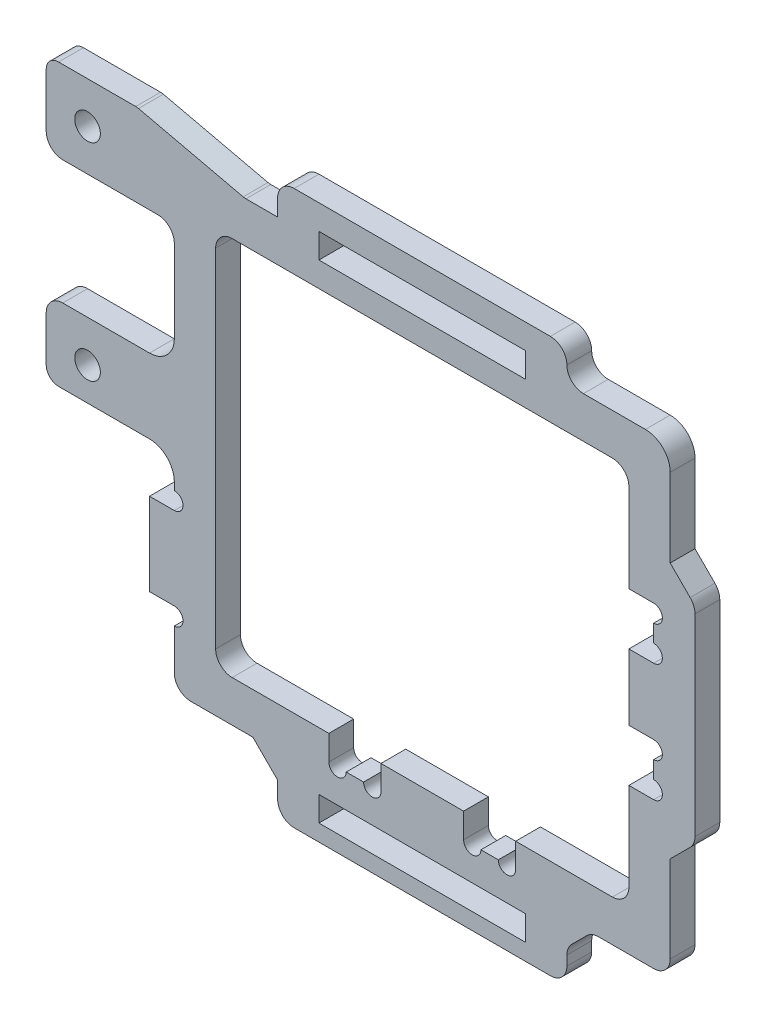
SolidWorks part; units mm, degrees
material "玻纤板"
ref_plane "前视基准面" through (0, 0, 0) normal (0, 0, 1) x (1, 0, 0)
ref_plane "上视基准面" through (0, 0, 0) normal (0, 1, 0) x (1, 0, 0)
ref_plane "右视基准面" through (0, 0, 0) normal (1, 0, 0) x (0, 0, -1)
sketch "草图1" plane through (0, 0, 0) normal (0, 0, 1) x (1, 0, 0)
  line L0 (-45.5, 31) -> (-45.5, 21)
  line L1 (25, -23) -> (11.3, -23)
  line L2 (25, -23) -> (25, -10.3)
  line L3 (25, 23) -> (-25, 23)
  line L4 (-25, -23) -> (-25, -11.2)
  line L5 (25, -23) -> (-25, 23) construction
  line L6 (25, 23) -> (-25, -23) construction
  line L7 (-45.5, 21) -> (-30, 21)
  line L8 (-30, 21) -> (-30, 15.2)
  line L9 (-30.5, 6) -> (-45.5, 6)
  line L11 (-35.5, -28) -> (-20.5, -28) construction
  line L12 (30, -28) -> (30, -23)
  line L13 (30, 28) -> (17.5, 28)
  line L14 (-5, -23) -> (-5, -26)
  line L15 (-5, -26) -> (-11.3, -26)
  line L16 (-11.3, -26) -> (-11.3, -23)
  line L17 (5, -23) -> (5, -26)
  line L18 (5, -26) -> (11.3, -26)
  line L19 (11.3, -26) -> (11.3, -23)
  line L20 (0, 0) -> (0, -12.9051) construction
  line L21 (-20.5, -28) -> (-17.5, -31) construction
  line L22 (-17.5, -31) -> (17.5, -31) construction
  line L23 (17.5, -31) -> (20.5, -28)
  line L24 (20.5, -28) -> (30, -28)
  line L25 (-11.3, -23) -> (-25, -23)
  line L26 (5, -23) -> (-5, -23)
  line L27 (25, 4) -> (28, 4)
  line L28 (28, 4) -> (28, 10.3)
  line L29 (28, 10.3) -> (25, 10.3)
  line L30 (25, -4) -> (28, -4)
  line L31 (28, -4) -> (28, -10.3)
  line L32 (28, -10.3) -> (25, -10.3)
  line L33 (0, 0) -> (16, 0) construction
  line L34 (30, 15.5) -> (33, 12.5)
  line L35 (33, 12.5) -> (33, -12.5)
  line L36 (33, -12.5) -> (30, -15.5)
  line L37 (25, 10.3) -> (25, 23)
  line L38 (25, -4) -> (25, 4)
  line L39 (30, 15.5) -> (30, 28)
  line L44 (-30, -9) -> (-33, -9)
  line L45 (-33, -9) -> (-33, -19)
  line L46 (-33, -19) -> (-30, -19)
  line L48 (17.5, 32) -> (17.5, 28)
  line L49 (17.5, 32) -> (-17.5, 32)
  line L50 (-17.5, 32) -> (-17.5, 28)
  line L51 (-17.5, 28) -> (-30, 28) construction
  line L52 (17.5, -31) -> (17.5, -35)
  line L53 (-12.5, 26) -> (12.5, 26)
  line L54 (-12.5, 26) -> (-12.5, 29)
  line L55 (-12.5, 29) -> (12.5, 29)
  line L56 (12.5, 26) -> (12.5, 29)
  line L57 (-12.5, 26) -> (12.5, 29) construction
  line L58 (-12.5, 29) -> (12.5, 26) construction
  line L59 (-12.5, -33) -> (12.5, -33)
  line L60 (-12.5, -33) -> (-12.5, -30)
  line L61 (-12.5, -30) -> (12.5, -30)
  line L62 (12.5, -33) -> (12.5, -30)
  line L63 (-12.5, -33) -> (12.5, -30) construction
  line L64 (-12.5, -30) -> (12.5, -33) construction
  line L65 (17.5, -35) -> (-17.5, -35)
  line L66 (-17.5, -35) -> (-17.5, -31) construction
  line L67 (30, -18) -> (42, -18) construction
  line L68 (42, -18) -> (39.1132, -23) construction
  line L69 (39.1132, -23) -> (29.9669, -23) construction
  line L70 (30, -18) -> (30, -15.5)
  line L71 (-45.5, 6) -> (-45.5, -3)
  line L72 (-46.5, -35) -> (-35.5, -35) construction
  line L73 (-35.5, -35) -> (-35.5, -28) construction
  line L74 (-17.5, -31) -> (-20.5, -28)
  line L75 (-33, -14) -> (-30, -14) construction
  line L76 (-30, 28) -> (-30, 31) construction
  line L77 (-45.5, 31) -> (-34.5, 31)
  line L78 (-28.75, 28) -> (-28.75, 37) construction
  line L79 (-34.5, 31) -> (-21.5, 28)
  line L80 (-17.5, 28) -> (-28.75, 28) construction
  line L81 (-17.5, -35) -> (-17.5, -31)
  line L82 (-17.5, -31) -> (-24, -31)
  line L83 (-20.5, -28) -> (-30, -28)
  line L84 (-30, -19) -> (-30, -28)
  line L85 (-30, -3) -> (-45.5, -3)
  line L86 (-17.5, 28) -> (-21.5, 28)
  line L88 (-30, 15.2) -> (-30, 6)
  line L89 (-30, 6) -> (-30.5, 6)
  line L92 (-30, -3) -> (-30, -9)
  line L93 (-25, 11.2) -> (-28, 11.2) construction
  line L94 (-28, 11.2) -> (-28, 5) construction
  line L95 (-28, 5) -> (-25, 5) construction
  line L96 (-25, -5) -> (-28, -5) construction
  line L97 (-28, -5) -> (-28, -11.2) construction
  line L98 (-28, -11.2) -> (-25, -11.2) construction
  line L99 (-25, 11.2) -> (-25, 23)
  line L100 (-25, -5) -> (-25, 5)
  line L101 (-30, 15.2) -> (-30.5, 15.2) construction
  line L102 (-30.5, 15.2) -> (-30.5, 6) construction
  line L103 (-24.2, 0) -> (-25, 0) construction
  line L104 (30, -18) -> (30, -23)
  line L105 (-25, -11.2) -> (-25, -5)
  line L106 (-25, 5) -> (-25, 11.2)
  circle A0 centre (-40.5, 26) radius 1.55
  circle A1 centre (-40.5, 1) radius 1.55
  circle A2 centre (-6.05, -26) radius 1.05
  circle A3 centre (6.05, -26) radius 1.05
  circle A4 centre (-10.25, -26) radius 1.05
  circle A5 centre (10.25, -26) radius 1.05
  circle A6 centre (28, 9.25) radius 1.05
  circle A7 centre (28, 5.05) radius 1.05
  circle A8 centre (28, -5.05) radius 1.05
  circle A9 centre (28, -9.25) radius 1.05
  circle A11 centre (-30, -20.05) radius 1.05
  circle A12 centre (-30, -7.95) radius 1.05
  circle A13 centre (-28, 6.05) radius 1.05 construction
  circle A14 centre (-28, -6.05) radius 1.05 construction
  circle A15 centre (-24.2, 0) radius 2 construction
  point P0 (0, 0)
  point P69 (0, 27.5)
  point P78 (0, -31.5)
  dimension "D10" = 3.1
  dimension "D16" = 2.1
  dimension "D64" = 4
  dimension "D1" = 46
  dimension "D2" = 50
  dimension "D3" = 5
  dimension "D4" = 5
  dimension "D5" = 5
  dimension "D6" = 5
  dimension "D7" = 14
  dimension "D8" = 5
  dimension "D9" = 5
  dimension "D11" = 25
  dimension "D12" = 26
  dimension "D13" = 3
  dimension "D14" = 6.3
  dimension "D15" = 10
  dimension "D17" = 35
  dimension "D18" = 45
  dimension "D19" = 5
  dimension "D20" = 8
  dimension "D21" = 6.3
  dimension "D22" = 3
  dimension "D23" = 5
  dimension "D24" = 25
  dimension "D25" = 45
  dimension "D26" = 3
  dimension "D27" = 10
  dimension "D28" = 3
  dimension "D29" = 3
  dimension "D30" = 3
  dimension "D31" = 5
  dimension "D32" = 5
  dimension "D33" = 25
  dimension "D34" = 4
  dimension "D35" = 3
  dimension "D36" = 25
  dimension "D37" = 2
  dimension "D38" = 5
  dimension "D39" = 12
  dimension "D40" = 60
  dimension "D41" = 18
  dimension "D42" = 11
  dimension "D43" = 5
  dimension "D44" = 7.5
  dimension "D45" = 5
  dimension "D46" = 6
  dimension "D47" = 1.25
  dimension "D48" = 5
  dimension "D50" = 4
  dimension "D51" = 5
  dimension "D52" = 4
  dimension "D55" = 3
  dimension "D56" = 10
  dimension "D57" = 6.2
  dimension "D58" = 6.2
  dimension "D59" = 5
  dimension "D61" = 3
  dimension "D62" = 5.5
  dimension "D63" = 4
  dimension "D65" = 0.8
extrude "凸台-拉伸1" add sketch "草图1" along normal blind 3 contours L23 L24 L12 L13 L0 L7 L8 L9 L11 L21 L22 A5 L18 A3 L17 L26 L14 A2 L15 A4 L16 L25 L4 L3 L2 L1 L19 A1 A0 region at (-40, 29.968, 0)
fillet "圆角2" radius 3 1 edges at (30, 28, 1.5)
fillet "圆角4" radius 2 1 edges at (-30, 21, 1.5)
fillet "圆角5" radius 1.5 4 edges at (-21.5, 28, 1.5) (-34.5, 31, 1.5) (-45.5, 31, 1.5) (-45.5, -3, 1.5)
fillet "圆角6" radius 3 2 edges at (-30, -3, 1.5) (-30, 6, 1.5)
fillet "圆角1" radius 2 17 edges at (-25, -23, 1.5) (25, -23, 1.5) (25, 23, 1.5) (-25, 23, 1.5) (33, 12.5, 1.5) (33, -12.5, 1.5) (17.5, -35, 1.5) (-17.5, 32, 1.5) (17.5, 28, 1.5) (17.5, 32, 1.5) (-45.5, 21, 1.5) (-45.5, 6, 1.5) (-17.5, -35, 1.5) (17.5, -31, 1.5) (20.5, -28, 1.5) (30, -28, 1.5) (-30, -28, 1.5)
